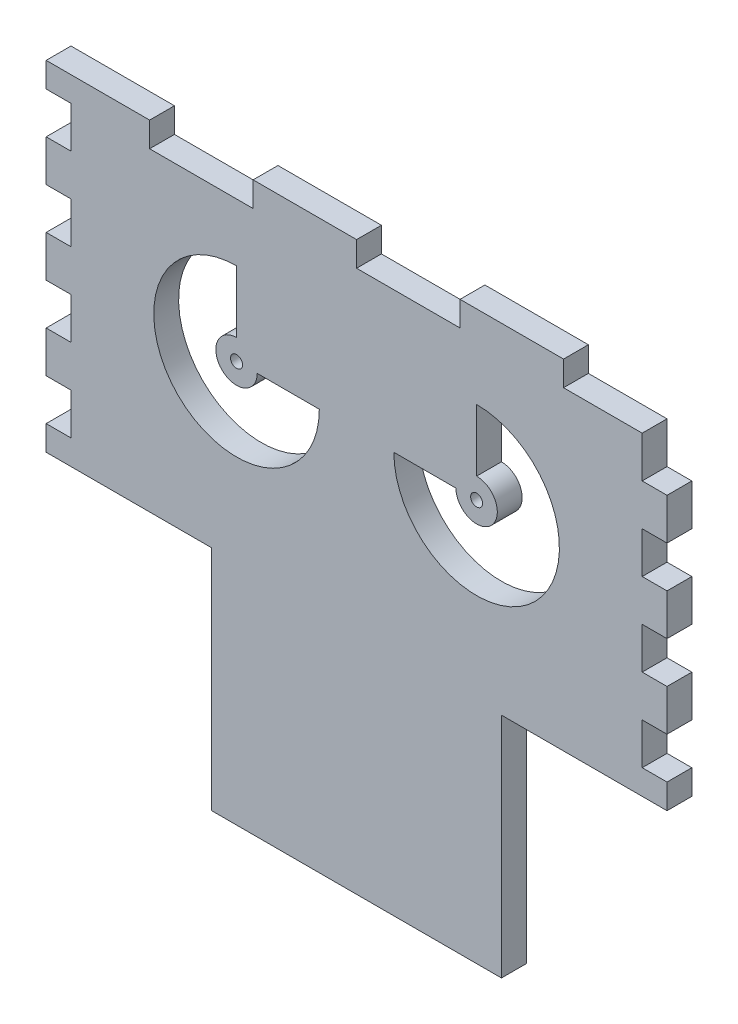
SolidWorks part; units mm, degrees
material "Pine"
ref_plane "Front Plane" through (0, 0, 0) normal (0, 0, 1) x (1, 0, 0)
ref_plane "Top Plane" through (0, 0, 0) normal (0, 1, 0) x (1, 0, 0)
ref_plane "Right Plane" through (0, 0, 0) normal (1, 0, 0) x (0, 0, -1)
sketch "Sketch1" plane through (0, 0, 0) normal (0, 0, 1) x (1, 0, 0)
  line L1 (75, -41) -> (-75, -41)
  line L2 (75, -41) -> (75, 41)
  line L3 (75, 41) -> (-75, 41)
  line L4 (-75, -41) -> (-75, 41)
  line L5 (75, -41) -> (-75, 41) construction
  line L6 (75, 41) -> (-75, -41) construction
  line L7 (-35, -41) -> (35, -41)
  line L8 (-35, -41) -> (-35, -96)
  line L9 (-35, -96) -> (35, -96)
  line L10 (35, -41) -> (35, -96)
  point P0 (0, 0)
  point P10 (0, -96)
  dimension "D1" = 150
  dimension "D2" = 82
  dimension "D3" = 55
  dimension "D4" = 70
  dimension "D5" = 0
extrude "Boss-Extrude1" add sketch "Sketch1" along normal blind 6 contours L10 L1 L8 L9 | L4 L1 L2 L3 region at (0, 0, 0) region at (0, -68.5, 0)
sketch "Sketch2" plane through (0, 0, 6) normal (0, 0, 1) x (1, 0, 0)
  line L0 (-75, -41) -> (-75, 41) construction
  line L1 (-75, 35) -> (-69, 35)
  line L2 (-75, 35) -> (-75, 25)
  line L3 (-75, 25) -> (-69, 25)
  line L4 (-69, 35) -> (-69, 25)
  line L5 (75, 41) -> (-75, 41) construction
  line L6 (69, 35) -> (69, 25)
  line L7 (69, 35) -> (75, 35)
  line L8 (75, 35) -> (75, 25)
  line L9 (69, 25) -> (75, 25)
  line L10 (69, 15) -> (69, 5)
  line L11 (69, 15) -> (75, 15)
  line L12 (75, 15) -> (75, 5)
  line L13 (69, 5) -> (75, 5)
  line L14 (-75, 15) -> (-75, 5)
  line L15 (-75, 15) -> (-69, 15)
  line L16 (-69, 15) -> (-69, 5)
  line L17 (-75, 5) -> (-69, 5)
  line L18 (-75, -5) -> (-75, -15)
  line L19 (-75, -5) -> (-69, -5)
  line L20 (-69, -5) -> (-69, -15)
  line L21 (-75, -15) -> (-69, -15)
  line L22 (69, -5) -> (69, -15)
  line L23 (69, -5) -> (75, -5)
  line L24 (75, -5) -> (75, -15)
  line L25 (69, -15) -> (75, -15)
  line L26 (-75, -25) -> (-75, -35)
  line L27 (-75, -25) -> (-69, -25)
  line L28 (-69, -25) -> (-69, -35)
  line L29 (-75, -35) -> (-69, -35)
  line L30 (69, -25) -> (69, -35)
  line L31 (69, -25) -> (75, -25)
  line L32 (75, -25) -> (75, -35)
  line L33 (69, -35) -> (75, -35)
  dimension "D1" = 6
  dimension "D2" = 10
  dimension "D3" = 6
  dimension "D4" = 2
  dimension "D5" = 4
extrude "Cut-Extrude1" cut sketch "Sketch2" against normal blind 10
sketch "Sketch3" plane through (0, 0, 6) normal (0, 0, 1) x (1, 0, 0)
  line L0 (-9, 1) -> (-24, 1)
  line L1 (-29, 21) -> (-29, 6)
  line L2 (-35, -41) -> (-75, -41) construction
  line L3 (9, 1) -> (24, 1)
  line L4 (29, 21) -> (29, 6)
  line L26 (0, -55) -> (0, 55) construction
  circle A0 centre (-29, 1) radius 1.45
  circle A4 centre (29, 1) radius 1.45
  arc A7 (-9, 1) -> (-29, 21) centre (-29, 1) cw
  arc A8 (-24, 1) -> (-29, 6) centre (-29, 1) cw
  arc A9 (9, 1) -> (29, 21) centre (29, 1) ccw
  arc A10 (24, 1) -> (29, 6) centre (29, 1) ccw
  dimension "D2" = 2.9
  dimension "D3" = 20
  dimension "D4" = 20
  dimension "D1" = 29
  dimension "D5" = 20
  dimension "D6" = 15
  dimension "D7" = 42
extrude "Cut-Extrude2" cut sketch "Sketch3" against normal blind 6
sketch "Sketch4" plane through (0, 0, 6) normal (0, 0, 1) x (1, 0, 0)
  line L0 (25, 41) -> (25, 35)
  line L1 (75, 41) -> (50, 41)
  line L2 (75, 41) -> (75, 35)
  line L3 (75, 35) -> (50, 35)
  line L4 (50, 41) -> (50, 35)
  line L5 (25, 41) -> (0, 41)
  line L6 (0, 41) -> (0, 35)
  line L7 (25, 35) -> (0, 35)
  line L8 (-25, 41) -> (-25, 35)
  line L9 (-25, 41) -> (-50, 41)
  line L10 (-50, 41) -> (-50, 35)
  line L11 (-25, 35) -> (-50, 35)
  dimension "D1" = 25
  dimension "D2" = 6
  dimension "D3" = 3
extrude "Cut-Extrude3" cut sketch "Sketch4" against normal blind 6
